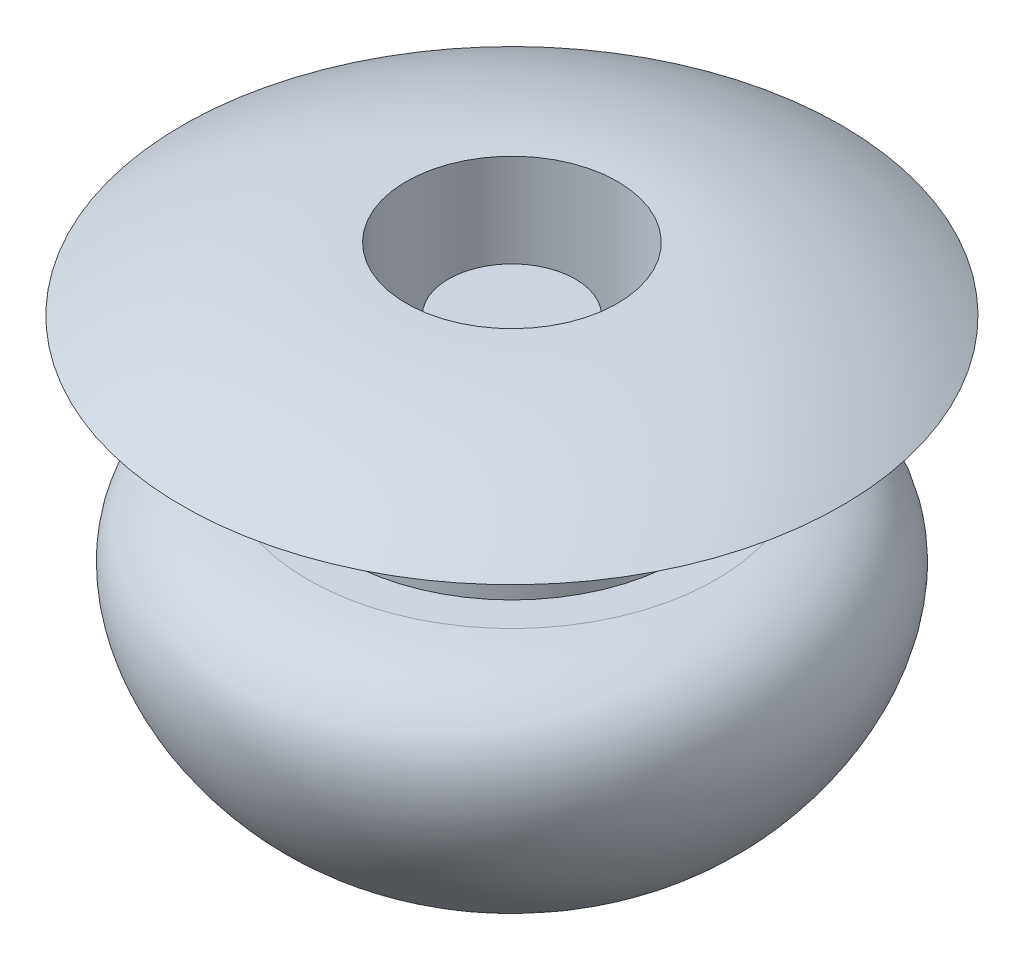
SolidWorks part; units mm, degrees
material "AISI 316 Stal nierdzewna odprężona (SS)"
ref_plane "Płaszczyzna przednia" through (0, 0, 0) normal (0, 0, 1) x (1, 0, 0)
ref_plane "Płaszczyzna górna" through (0, 0, 0) normal (0, 1, 0) x (1, 0, 0)
ref_plane "Płaszczyzna prawa" through (0, 0, 0) normal (1, 0, 0) x (0, 0, -1)
sketch "Szkic1" plane through (0, 0, 0) normal (1, 0, 0) x (0, 0, -1)
  line L1 (0, 0) -> (-0.75, 0)
  line L2 (-0.75, 0) -> (-0.75, -1.7007)
  line L3 (-0.75, -1.7007) -> (-1.25, -1.7007)
  line L4 (-1.25, -1.7007) -> (-1.25, 0.75)
  line L5 (-3.9, 0) -> (-2, 0)
  line L6 (-2, 0) -> (-2, -1.5)
  line L7 (-2, -1.5) -> (-2.4139, -1.5)
  line L8 (0, 0) -> (0, 0.4842) construction
  line L9 (0, -1.7007) -> (0, 0)
  line L10 (0, -1.7007) -> (0, -3.2007)
  line L11 (65.5531, -1.5) -> (69.5531, -1.5) construction
  arc A0 (-1.25, 0.75) -> (-3.9, 0) centre (-1.25, -4.3067) ccw
  ellipse E0 centre (0, -2.4507) end of major axis (-1.75, -2.4507) minor radius 0.75 (-0.956, -3.0789) -> (0, -3.2007) ccw
  spline S0 degree 3 poles (-2.4139, -1.5) (-3.8675, -1.6697) (-3.5289, -3.802) (-1.084, -5.3735) (-0.2718, -3.3749) (-0.956, -3.0789) knots 0 0 0 0 0.464993 0.721928 1 1 1 1
  dimension "D1" = 7.8
  dimension "D2" = 2.5
  dimension "D3" = 4
  dimension "D4" = 0.75
  dimension "D5" = 1.5
  dimension "D6" = 1.5
  dimension "D7" = 3.5
  dimension "D8" = 3.1855
  dimension "D9" = 2.5026
  dimension "D10" = 1.9
  dimension "D11" = 1.5789
  dimension "D12" = 0.5792
  dimension "D13" = 4.8278
  dimension "D14" = 3.3858
  dimension "D15" = 2.8395
  dimension "D16" = 1.25
  dimension "D17" = 0.6409
  dimension "D18" = 0.956
revolve "Obrót1" add sketch "Szkic1" angle 360 about L8
